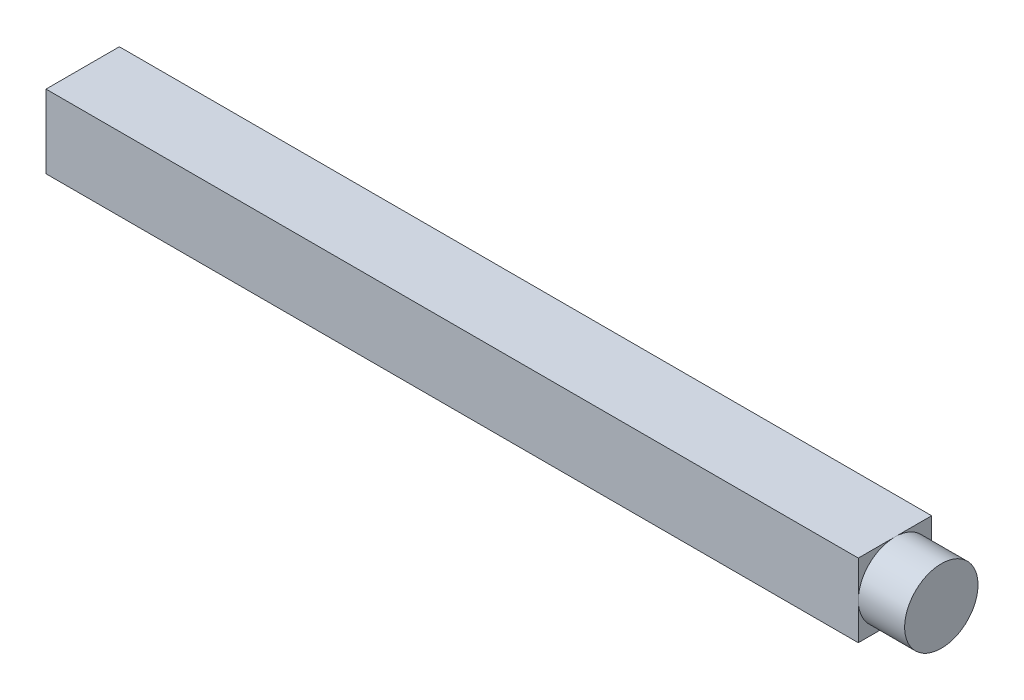
SolidWorks part; units mm, degrees
ref_plane "Front Plane" through (0, 0, 0) normal (0, 0, 1) x (1, 0, 0)
ref_plane "Top Plane" through (0, 0, 0) normal (0, 1, 0) x (1, 0, 0)
ref_plane "Right Plane" through (0, 0, 0) normal (1, 0, 0) x (0, 0, -1)
sketch "Sketch1" plane through (0, 0, 0) normal (1, 0, 0) x (0, 0, -1)
  line L1 (-3.175, -3.175) -> (3.175, -3.175)
  line L2 (-3.175, -3.175) -> (-3.175, 3.175)
  line L3 (-3.175, 3.175) -> (3.175, 3.175)
  line L4 (3.175, -3.175) -> (3.175, 3.175)
  line L5 (-3.175, -3.175) -> (3.175, 3.175) construction
  line L6 (-3.175, 3.175) -> (3.175, -3.175) construction
  point P0 (0, 0)
  dimension "D1" = 6.35
extrude "Boss-Extrude1" add sketch "Sketch1" along normal up to surface (74.3375 mm away)
ref_axis "Axis1" through (73.3425, 0, 0) along (-1, 0, 0)
sketch "Sketch2" plane through (74.3375, 0, 0) normal (1, 0, 0) x (0, 0, -1)
  line L16 (-3.302, -3.302) -> (3.302, -3.302)
  line L17 (3.302, -3.302) -> (3.302, 3.302)
  line L18 (3.302, 3.302) -> (-3.302, 3.302)
  line L19 (-3.302, 3.302) -> (-3.302, -3.302)
  line L20 (-3.302, -3.302) -> (3.302, -3.302)
  line L21 (3.302, -3.302) -> (3.302, 3.302)
  line L22 (3.302, 3.302) -> (-3.302, 3.302)
  line L23 (-3.302, 3.302) -> (-3.302, -3.302)
  circle A0 centre (0, 0) radius 3.175
  dimension "D1" = 6.35
  dimension "D2" = 0.127
extrude "Cut-Extrude1" cut sketch "Sketch2" against normal up to surface (4.0132 mm away)
